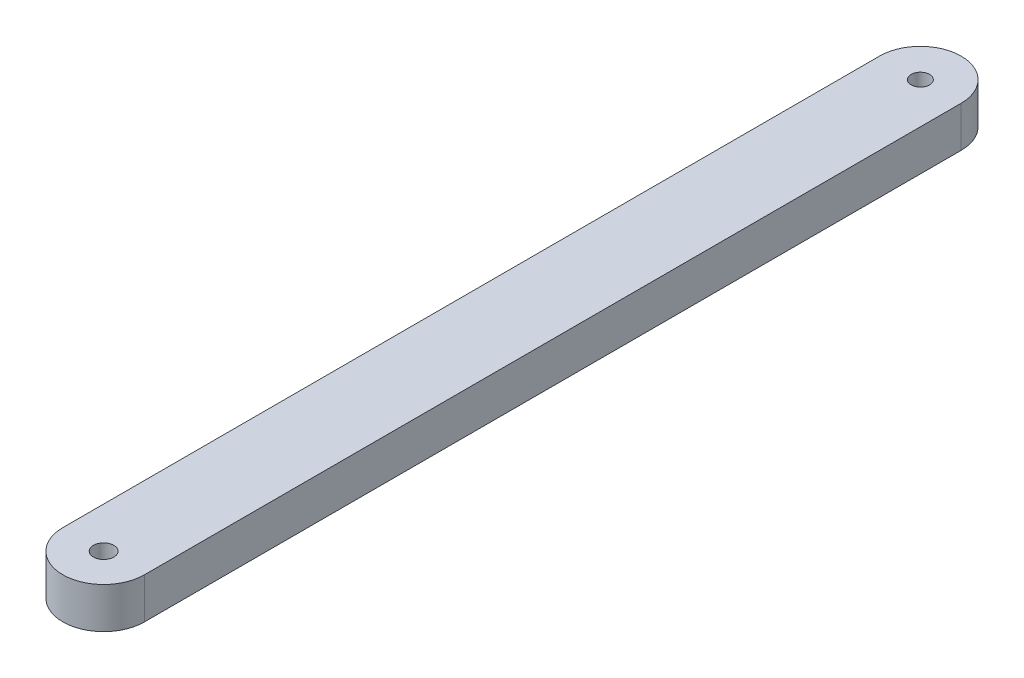
SolidWorks part; units mm, degrees
ref_plane "Front Plane" through (0, 0, 0) normal (0, 0, 1) x (1, 0, 0)
ref_plane "Top Plane" through (0, 0, 0) normal (0, 1, 0) x (1, 0, 0)
ref_plane "Right Plane" through (0, 0, 0) normal (1, 0, 0) x (0, 0, -1)
sketch "Sketch1" plane through (0, 0, 0) normal (0, 1, 0) x (1, 0, 0)
  line L0 (-10, 100) -> (10, 100) construction
  line L2 (10, -100) -> (10, 100)
  line L4 (-10, -100) -> (-10, 100)
  line L5 (10, -100) -> (-10, 100) construction
  line L6 (10, 100) -> (-10, -100) construction
  line L8 (-1.5875, 98.4125) -> (1.5875, 98.4125)
  line L9 (-1.5875, 98.4125) -> (-1.5875, 101.5875)
  line L10 (-1.5875, 101.5875) -> (1.5875, 101.5875)
  line L11 (1.5875, 98.4125) -> (1.5875, 101.5875)
  line L12 (-1.5875, 98.4125) -> (1.5875, 101.5875) construction
  line L13 (-1.5875, 101.5875) -> (1.5875, 98.4125) construction
  arc A0 (-10, 100) -> (10, 100) centre (0, 100) cw
  arc A1 (10, -100) -> (-10, -100) centre (0, -100) cw
  circle A2 centre (0, -100) radius 2.5
  circle A3 centre (0, 100) radius 2.2451
  point P0 (0, 0)
  dimension "D3" = 5
  dimension "D1" = 200
  dimension "D2" = 20
  dimension "D4" = 3.175
extrude "Boss-Extrude1" add sketch "Sketch1" along normal blind 10 contours A1 L2 A0 L4 A3 A2 region at (0, 0, -0.0888)
